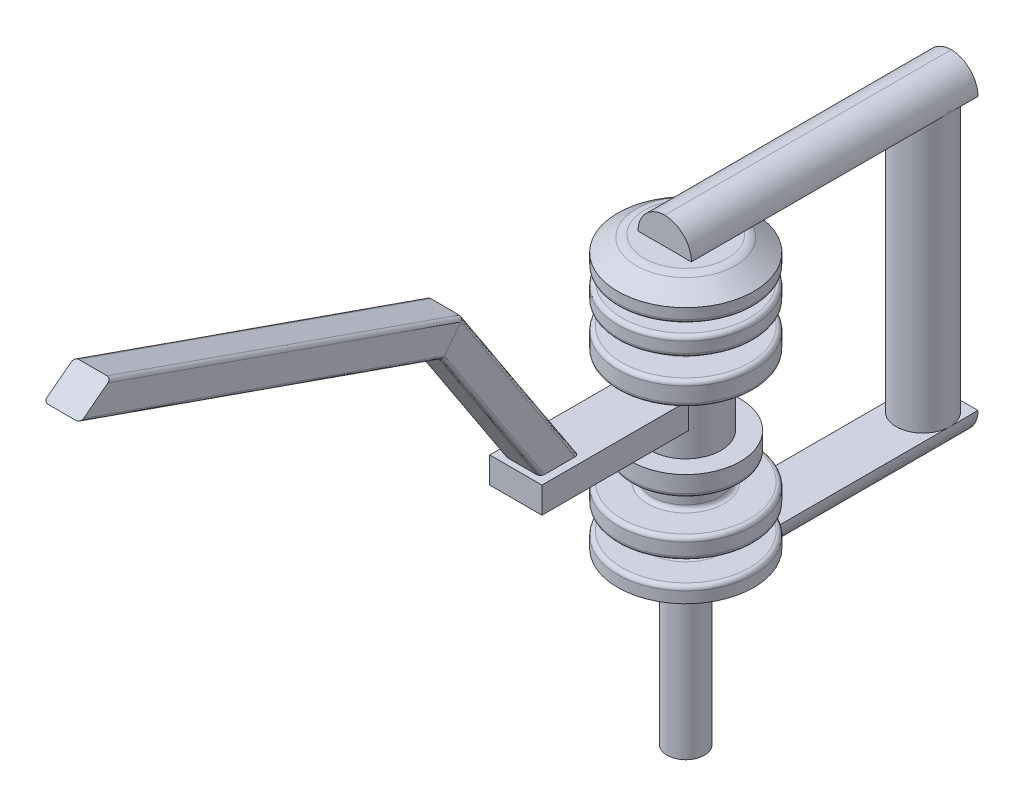
SolidWorks part; units mm, degrees
ref_plane "Alzado" through (0, 0, 0) normal (0, 0, 1) x (1, 0, 0)
ref_plane "Planta" through (0, 0, 0) normal (0, 1, 0) x (1, 0, 0)
ref_plane "Vista lateral" through (0, 0, 0) normal (1, 0, 0) x (0, 0, -1)
sketch "Croquis2" plane through (0, 0, 0) normal (0, 0, 1) x (1, 0, 0)
  line L0 (0, 0) -> (0, 200) construction
  line L1 (0, 0) -> (50, 0)
  line L2 (0, 200) -> (30.6231, 200)
  line L3 (36.3707, 198.1832) -> (50, 188.6104)
  line L4 (50, 188.6104) -> (50, 181.0536)
  line L5 (47, 178.0536) -> (28, 178.0536)
  line L6 (25, 175.0536) -> (25, 173.2552)
  line L7 (28, 170.2552) -> (47, 170.2552)
  line L8 (50, 167.2552) -> (50, 159.4928)
  line L9 (47, 156.4928) -> (28, 156.4928)
  line L10 (25, 153.4928) -> (25, 144.7408)
  line L11 (28, 141.7408) -> (47, 141.7408)
  line L12 (50, 138.7408) -> (50, 127.7191)
  line L13 (47, 124.7191) -> (25.8787, 124.7191)
  line L14 (25.8787, 124.7191) -> (25.8787, 75.2457)
  line L15 (25.8787, 75.2457) -> (40, 75.2457)
  line L16 (0, 0) -> (0, 200)
  line L18 (50, 0) -> (50, 8.1795)
  line L19 (47, 11.1795) -> (28, 11.1795)
  line L20 (25, 14.1795) -> (25, 24.196)
  line L21 (28, 27.196) -> (47, 27.196)
  line L22 (50, 30.196) -> (50, 39.3228)
  line L23 (47, 42.3228) -> (28, 42.3228)
  line L24 (25, 45.3228) -> (25, 57.1189)
  line L25 (28, 60.1189) -> (37, 60.1189)
  line L26 (40, 63.1189) -> (40, 75.2457)
  arc A2 (30.6231, 200) -> (36.3707, 198.1832) centre (30.6231, 190) cw
  arc A3 (50, 8.1795) -> (47, 11.1795) centre (47, 8.1795) ccw
  arc A4 (28, 11.1795) -> (25, 14.1795) centre (28, 14.1795) cw
  arc A5 (25, 24.196) -> (28, 27.196) centre (28, 24.196) cw
  arc A6 (47, 27.196) -> (50, 30.196) centre (47, 30.196) ccw
  arc A7 (50, 39.3228) -> (47, 42.3228) centre (47, 39.3228) ccw
  arc A8 (28, 42.3228) -> (25, 45.3228) centre (28, 45.3228) cw
  arc A9 (25, 57.1189) -> (28, 60.1189) centre (28, 57.1189) cw
  arc A10 (37, 60.1189) -> (40, 63.1189) centre (37, 63.1189) ccw
  arc A11 (50, 127.7191) -> (47, 124.7191) centre (47, 127.7191) cw
  arc A12 (47, 141.7408) -> (50, 138.7408) centre (47, 138.7408) cw
  arc A13 (25, 144.7408) -> (28, 141.7408) centre (28, 144.7408) ccw
  arc A14 (28, 156.4928) -> (25, 153.4928) centre (28, 153.4928) ccw
  arc A15 (50, 159.4928) -> (47, 156.4928) centre (47, 159.4928) cw
  arc A16 (47, 170.2552) -> (50, 167.2552) centre (47, 167.2552) cw
  arc A17 (50, 181.0536) -> (47, 178.0536) centre (47, 181.0536) cw
  arc A18 (28, 178.0536) -> (25, 175.0536) centre (28, 175.0536) ccw
  arc A19 (25, 173.2552) -> (28, 170.2552) centre (28, 173.2552) ccw
  dimension "D4" = 3
  dimension "D1" = 200
  dimension "D2" = 50
revolve "Revolución2" add sketch "Croquis2" angle 360 about L0
sketch "Croquis3" plane through (0, 200, 0) normal (0, 1, 0) x (1, 0, 0)
  line L0 (0, 0) -> (0, 89.9071) construction
  line L2 (-19.6293, -15.482) -> (19.6293, -15.482)
  line L3 (-19.6293, -15.482) -> (-19.6293, 195.2962)
  line L4 (-19.6293, 195.2962) -> (19.6293, 195.2962)
  line L5 (19.6293, -15.482) -> (19.6293, 195.2962)
  line L6 (-19.6293, -15.482) -> (19.6293, 195.2962) construction
  line L7 (-19.6293, 195.2962) -> (19.6293, -15.482) construction
extrude "Saliente-Extruir1" add sketch "Croquis3" along normal blind 20
fillet "Redondeo1" radius 20 2 edges at (-19.6293, 220, -89.9071) (19.6293, 220, -89.9071)
sketch "Croquis4" plane through (0, 0, 0) normal (0, -1, 0) x (1, 0, 0)
  line L0 (-19.6293, -195.2962) -> (19.6293, -195.2962)
  line L1 (19.6293, -195.2962) -> (19.6293, 0)
  line L2 (19.6293, 0) -> (-19.6293, 0)
  line L3 (-19.6293, 0) -> (-19.6293, -195.2962)
extrude "Saliente-Extruir2" add sketch "Croquis4" along normal blind 20
fillet "Redondeo2" radius 20 2 edges at (-19.6293, -20, -97.6481) (19.6293, -20, -97.6481)
sketch "Croquis5" plane through (0, 0, 0) normal (0, 1, 0) x (1, 0, 0)
  line L0 (0, -15.482) -> (0, 195.2962) construction
  circle A0 centre (0, 174.4713) radius 19.6293
extrude "Saliente-Extruir3" add sketch "Croquis5" along normal blind 201
sketch "Croquis6" plane through (0, 0, 0) normal (0, 0, 1) x (1, 0, 0)
  line L1 (-19.212, 112.3867) -> (19.212, 112.3867)
  line L2 (-19.212, 112.3867) -> (-19.212, 93.1747)
  line L3 (-19.212, 93.1747) -> (19.212, 93.1747)
  line L4 (19.212, 112.3867) -> (19.212, 93.1747)
  line L5 (-19.212, 112.3867) -> (19.212, 93.1747) construction
  line L6 (-19.212, 93.1747) -> (19.212, 112.3867) construction
  point P0 (0, 102.7807)
extrude "Saliente-Extruir4" add sketch "Croquis6" along normal blind 125
sketch "Croquis7" plane through (0, 112.3867, 0) normal (0, 1, 0) x (1, 0, 0)
  line L1 (10.4384, -91.8481) -> (-10.4384, -91.8481)
  line L2 (13.4384, -94.8481) -> (13.4384, -117.2959)
  line L3 (10.4384, -120.2959) -> (-10.4384, -120.2959)
  line L4 (-13.4384, -94.8481) -> (-13.4384, -117.2959)
  line L5 (13.4384, -91.8481) -> (-13.4384, -120.2959) construction
  line L6 (13.4384, -120.2959) -> (-13.4384, -91.8481) construction
  arc A0 (-10.4384, -91.8481) -> (-13.4384, -94.8481) centre (-10.4384, -94.8481) ccw
  arc A1 (-10.4384, -120.2959) -> (-13.4384, -117.2959) centre (-10.4384, -117.2959) cw
  arc A2 (13.4384, -117.2959) -> (10.4384, -120.2959) centre (10.4384, -117.2959) cw
  arc A3 (10.4384, -91.8481) -> (13.4384, -94.8481) centre (10.4384, -94.8481) cw
  point P0 (0, -106.072)
  dimension "D1" = 3
sketch3d "Croquis3D1"
  line L0 (0, 112.3867, 106.072) -> (0, 232.4894, 184.843)
  line L1 (0, 232.4894, 184.843) -> (0, 324.4912, 447.3591)
  point P4 (0, 292.1653, 379.9098)
  point P5 (0, 324.4912, 447.3591)
sweep "Barrer1" add profiles "Croquis7" path "Croquis3D1"
sketch "Croquis8" plane through (0, 0, 0) normal (0, -1, 0) x (1, 0, 0)
  circle A0 centre (0, 0) radius 13.7
  dimension "D1" = 27.4
extrude "Saliente-Extruir5" add sketch "Croquis8" along normal blind 125
